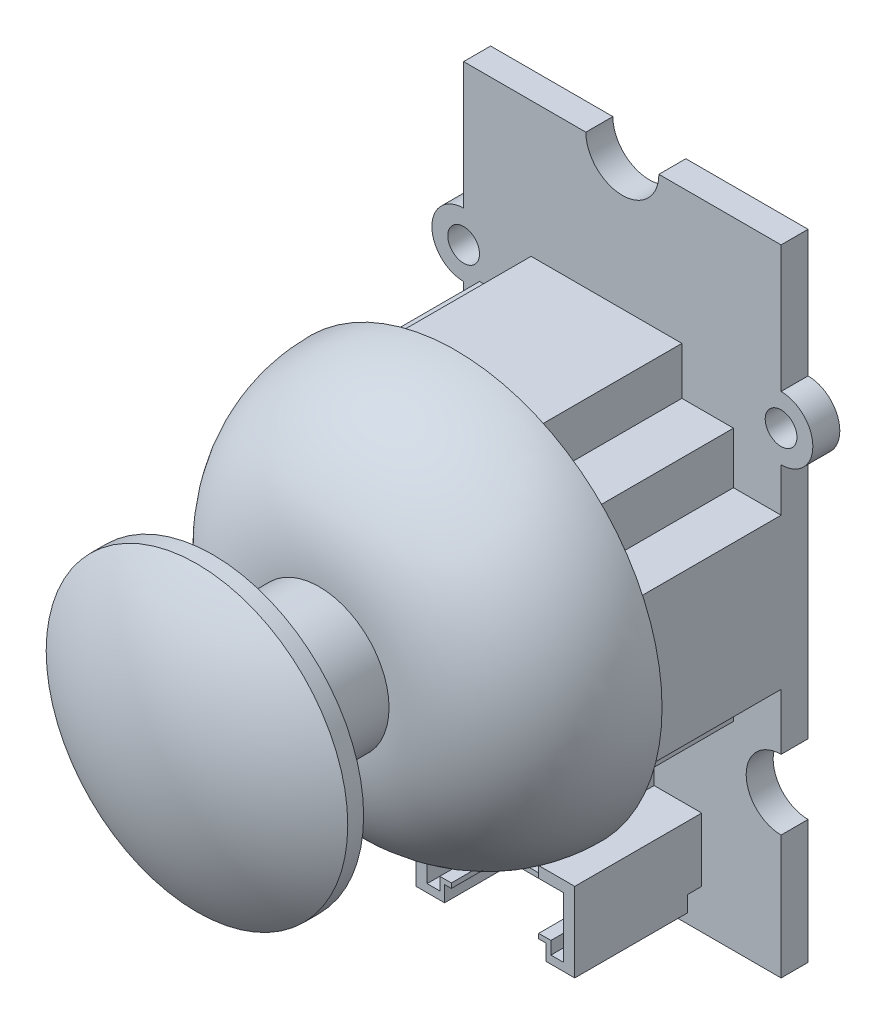
SolidWorks part; units mm, degrees
ref_plane "Plan de face" through (0, 0, 0) normal (0, 0, 1) x (1, 0, 0)
ref_plane "Plan de dessus" through (0, 0, 0) normal (0, 1, 0) x (1, 0, 0)
ref_plane "Plan de droite" through (0, 0, 0) normal (1, 0, 0) x (0, 0, -1)
sketch "Esquisse1" plane through (0, 0, 0) normal (0, 0, 1) x (1, 0, 0)
  line L0 (-11.4537, 10.8333) -> (8.5463, 10.8333) construction
  line L1 (-11.4537, 20.8333) -> (-3.7537, 20.8333)
  line L2 (-11.4537, 20.8333) -> (-11.4537, 12.8333)
  line L3 (-11.4537, -19.1667) -> (-3.4537, -19.1667)
  line L4 (8.5463, 20.8333) -> (8.5463, 12.8333)
  line L5 (-11.4537, -9.1667) -> (8.5463, -9.1667) construction
  line L6 (0.8463, 20.8333) -> (8.5463, 20.8333)
  line L7 (-11.4537, 8.8333) -> (-11.4537, -6.9667)
  line L8 (8.5463, 8.8333) -> (8.5463, -6.9667)
  line L9 (8.5463, -11.3667) -> (8.5463, -19.1667)
  line L10 (-11.4537, -11.3667) -> (-11.4537, -19.1667)
  line L11 (0.5463, -19.1667) -> (8.5463, -19.1667)
  arc A0 (-3.7537, 20.8333) -> (0.8463, 20.8333) centre (-1.4537, 20.8333) ccw
  arc A1 (-11.4537, 12.8333) -> (-11.4537, 8.8333) centre (-11.4537, 10.8333) ccw
  arc A2 (8.5463, 8.8333) -> (8.5463, 12.8333) centre (8.5463, 10.8333) ccw
  arc A3 (-11.4537, -11.3667) -> (-11.4537, -6.9667) centre (-11.4537, -9.1667) ccw
  arc A4 (8.5463, -6.9667) -> (8.5463, -11.3667) centre (8.5463, -9.1667) ccw
  arc A5 (-3.4537, -19.1667) -> (0.5463, -19.1667) centre (-1.4537, -19.1667) ccw
  circle A6 centre (-11.4537, 10.8333) radius 1
  circle A7 centre (8.5463, 10.8333) radius 1
  circle A8 centre (-1.4537, -19.1667) radius 1
  dimension "D3" = 10
  dimension "D1" = 20
  dimension "D2" = 40
  dimension "D4" = 20
extrude "Boss.-Extru.1" add sketch "Esquisse1" along normal blind 1.7
sketch "Esquisse2" plane through (0, 0, 1.7) normal (0, 0, 1) x (1, 0, 0)
  line L0 (-11.4537, -11.3667) -> (-11.4537, -19.1667) construction
  line L1 (-6.4537, -12.6667) -> (3.5463, -12.6667)
  line L2 (-6.4537, -12.6667) -> (-6.4537, -17.6667)
  line L3 (-6.4537, -17.6667) -> (3.5463, -17.6667)
  line L4 (3.5463, -12.6667) -> (3.5463, -17.6667)
  line L5 (-11.4537, -19.1667) -> (-3.4537, -19.1667) construction
  dimension "D1" = 10
  dimension "D2" = 5
  dimension "D3" = 5
  dimension "D4" = 1.5
extrude "Boss.-Extru.2" add sketch "Esquisse2" along normal blind 8
sketch "Esquisse3" plane through (0, -17.6667, 0) normal (0, -1, 0) x (1, 0, 0)
  line L0 (-6.4537, 1.7) -> (3.5463, 1.7)
  line L1 (3.5463, 1.7) -> (3.5463, 2.6)
  line L2 (3.5463, 9.7) -> (3.5463, 1.7) construction
  line L3 (3.5463, 2.6) -> (1.7463, 2.6)
  line L4 (-6.4537, 1.7) -> (-6.4537, 2.6)
  line L5 (-6.4537, 9.7) -> (-6.4537, 1.7) construction
  line L6 (-6.4537, 2.6) -> (-4.6537, 2.6)
  line L7 (-4.6537, 2.6) -> (-4.6537, 9.7)
  line L8 (-6.4537, 9.7) -> (3.5463, 9.7) construction
  line L9 (1.7463, 2.6) -> (1.7463, 9.7)
  line L10 (1.7463, 9.7) -> (-4.6537, 9.7)
  line L11 (-1.4537, 9.7) -> (-1.4537, 3.3853) construction
  line L12 (-3.4537, 6.4) -> (0.5463, 6.4)
  line L13 (-3.4537, 6.4) -> (-3.4537, 5)
  line L14 (-3.4537, 5) -> (0.5463, 5)
  line L15 (0.5463, 6.4) -> (0.5463, 5)
  dimension "D1" = 1.8
  dimension "D2" = 1.8
  dimension "D3" = 3.3
  dimension "D4" = 4
  dimension "D5" = 2
  dimension "D6" = 1.4
extrude "Enlèv. mat.-Extru.1" cut sketch "Esquisse3" against normal blind 1
chamfer "Chanfrein2" distance 1 angle 45 1 edges at (-1.4537, -17.6667, 6.4)
sketch "Esquisse4" plane through (0, -16.6667, 0) normal (0, -1, 0) x (1, 0, 0)
  line L0 (1.7463, 9.7) -> (-4.6537, 9.7) construction
  line L1 (-4.2268, 9.7) -> (1.2732, 9.7)
  line L2 (-4.2268, 9.7) -> (-4.2268, 6.4)
  line L3 (-4.2268, 6.4) -> (1.2732, 6.4)
  line L4 (1.2732, 9.7) -> (1.2732, 6.4)
  line L5 (-1.4768, 9.7) -> (-1.4768, 3.3072) construction
  dimension "D1" = 5.5
  dimension "D2" = 2.75
extrude "Enlèv. mat.-Extru.2" cut sketch "Esquisse4" against normal blind 1
sketch "Esquisse5" plane through (0, -15.6667, 0) normal (0, -1, 0) x (1, 0, 0)
  line L0 (1.2732, 6.4) -> (1.2732, 9.7) construction
  line L1 (-4.2268, 9.7) -> (1.2732, 9.7)
  line L2 (-4.2268, 9.7) -> (-4.2268, 8.2)
  line L3 (-4.2268, 8.2) -> (1.2732, 8.2)
  line L4 (1.2732, 9.7) -> (1.2732, 8.2)
  dimension "D1" = 1.5
extrude "Enlèv. mat.-Extru.3" cut sketch "Esquisse5" against normal blind 11
sketch "Esquisse6" plane through (0, 0, 9.7) normal (0, 0, 1) x (1, 0, 0)
  line L0 (-6.4537, -12.6667) -> (-6.4537, -16.6667) construction
  line L1 (-5.7537, -13.3667) -> (2.8463, -13.3667)
  line L2 (-5.7537, -13.3667) -> (-5.7537, -16.3667)
  line L3 (-4.9537, -16.3667) -> (2.0463, -16.3667)
  line L4 (2.8463, -13.3667) -> (2.8463, -16.3667)
  line L5 (3.5463, -16.6667) -> (3.5463, -12.6667) construction
  line L6 (3.5463, -12.6667) -> (-6.4537, -12.6667) construction
  line L7 (-5.7537, -16.3667) -> (-5.7537, -17.1667)
  line L8 (-5.7537, -17.1667) -> (-4.9537, -17.1667)
  line L9 (-4.9537, -17.1667) -> (-4.9537, -16.3667)
  line L10 (2.8463, -16.3667) -> (2.8463, -17.1667)
  line L11 (2.8463, -17.1667) -> (2.0463, -17.1667)
  line L12 (2.0463, -17.1667) -> (2.0463, -16.3667)
  dimension "D1" = 0.7
  dimension "D2" = 0.7
  dimension "D3" = 0.7
  dimension "D4" = 3
extrude "Enlèv. mat.-Extru.4" cut sketch "Esquisse6" against normal blind 7
sketch "Esquisse7" plane through (0, 0, 1.7) normal (0, 0, 1) x (1, 0, 0)
  line L0 (3.5463, -12.6667) -> (-6.4537, -12.6667) construction
  line L1 (-5.4537, -12.6667) -> (0.5463, -12.6667)
  line L2 (-5.4537, -12.6667) -> (-5.4537, -6.6667)
  line L3 (-5.4537, -6.6667) -> (0.5463, -6.6667)
  line L4 (0.5463, -12.6667) -> (0.5463, -6.6667)
  line L5 (-11.4537, -11.3667) -> (-11.4537, -19.1667) construction
  dimension "D1" = 6
  dimension "D2" = 6
  dimension "D3" = 6
extrude "Boss.-Extru.3" add sketch "Esquisse7" along normal blind 5
sketch "Esquisse8" plane through (0, 0, 6.7) normal (0, 0, 1) x (1, 0, 0)
  line L0 (-5.4537, -12.6667) -> (0.5463, -6.6667) construction
  circle A0 centre (-2.4537, -9.6667) radius 1.75
extrude "Boss.-Extru.4" add sketch "Esquisse8" along normal blind 1
sketch "Esquisse9" plane through (0, 0, 1.7) normal (0, 0, 1) x (1, 0, 0)
  line L0 (3.5463, -12.6667) -> (0.5463, -12.6667) construction
  line L1 (-10.4537, -6.6667) -> (5.5463, -6.6667)
  line L2 (-10.4537, -6.6667) -> (-10.4537, 9.3333)
  line L3 (-10.4537, 9.3333) -> (5.5463, 9.3333)
  line L4 (5.5463, -6.6667) -> (5.5463, 9.3333)
  line L5 (-11.4537, 8.8333) -> (-11.4537, -6.9667) construction
  dimension "D1" = 16
  dimension "D2" = 16
  dimension "D3" = 6
  dimension "D4" = 1
extrude "Boss.-Extru.5" add sketch "Esquisse9" along normal blind 12
sketch "Esquisse10" plane through (0, 0, 1.7) normal (0, 0, 1) x (1, 0, 0)
  line L0 (5.5463, 9.3333) -> (-10.4537, 9.3333) construction
  line L1 (-7.2037, 9.3333) -> (2.2963, 9.3333)
  line L2 (-7.2037, 9.3333) -> (-7.2037, 12.3333)
  line L3 (-7.2037, 12.3333) -> (2.2963, 12.3333)
  line L4 (2.2963, 9.3333) -> (2.2963, 12.3333)
  line L5 (5.5463, -6.6667) -> (5.5463, 9.3333) construction
  line L6 (5.5463, 6.0833) -> (8.5463, 6.0833)
  line L7 (5.5463, 6.0833) -> (5.5463, -3.4167)
  line L8 (5.5463, -3.4167) -> (8.5463, -3.4167)
  line L9 (8.5463, 6.0833) -> (8.5463, -3.4167)
  line L10 (-10.4537, 9.3333) -> (-10.4537, -6.6667) construction
  line L11 (-10.4537, -6.6667) -> (5.5463, -6.6667) construction
  dimension "D1" = 3
  dimension "D2" = 3
  dimension "D3" = 9.5
  dimension "D4" = 9.5
  dimension "D5" = 3.25
  dimension "D6" = 3.25
extrude "Boss.-Extru.6" add sketch "Esquisse10" along normal blind 12
sketch "Esquisse12" plane through (0, 0, 13.7) normal (0, 0, 1) x (1, 0, 0)
  line L1 (-16.9332, 14.561) -> (15.2642, 14.561)
  line L2 (-16.9332, 14.561) -> (-16.9332, -8.1718)
  line L3 (-16.9332, -8.1718) -> (15.2642, -8.1718)
  line L4 (15.2642, 14.561) -> (15.2642, -8.1718)
extrude "Enlèv. mat.-Extru.5" cut sketch "Esquisse12" against normal blind 2.5
sketch "Esquisse13" plane through (0, 0, 11.2) normal (0, 0, 1) x (1, 0, 0)
  line L0 (-10.4537, -6.6667) -> (5.5463, 9.3333) construction
  circle A0 centre (-2.4537, 1.3333) radius 13
extrude "Boss.-Extru.7" add sketch "Esquisse13" along normal blind 8.6
fillet "Congé1" radius 8.6 1 edges at (10.5463, 1.3333, 19.8)
sketch "Esquisse14" plane through (0, 0, 19.8) normal (0, 0, 1) x (1, 0, 0)
  circle A0 centre (-2.4537, 1.3333) radius 4.4
extrude "Boss.-Extru.8" add sketch "Esquisse14" along normal blind 6.7
sketch "Esquisse15" plane through (0, 0, 26.5) normal (0, 0, 1) x (1, 0, 0)
  circle A0 centre (-2.4537, 1.3333) radius 9.5
extrude "Boss.-Extru.9" add sketch "Esquisse15" along normal blind 1
dome "Dôme1" faces to dome 1 distance 3 reverse direction no elliptical dome no face at (7.0463, 1.3333, 27.5) parameters "D1"=3
sketch "Esquisse18" plane through (0, -6.6667, 0) normal (0, -1, 0) x (1, 0, 0)
  circle A0 centre (-2.4537, 9.1994) radius 1.4994
extrude "Boss.-Extru.11" add sketch "Esquisse18" along normal blind 3.6 separate body
